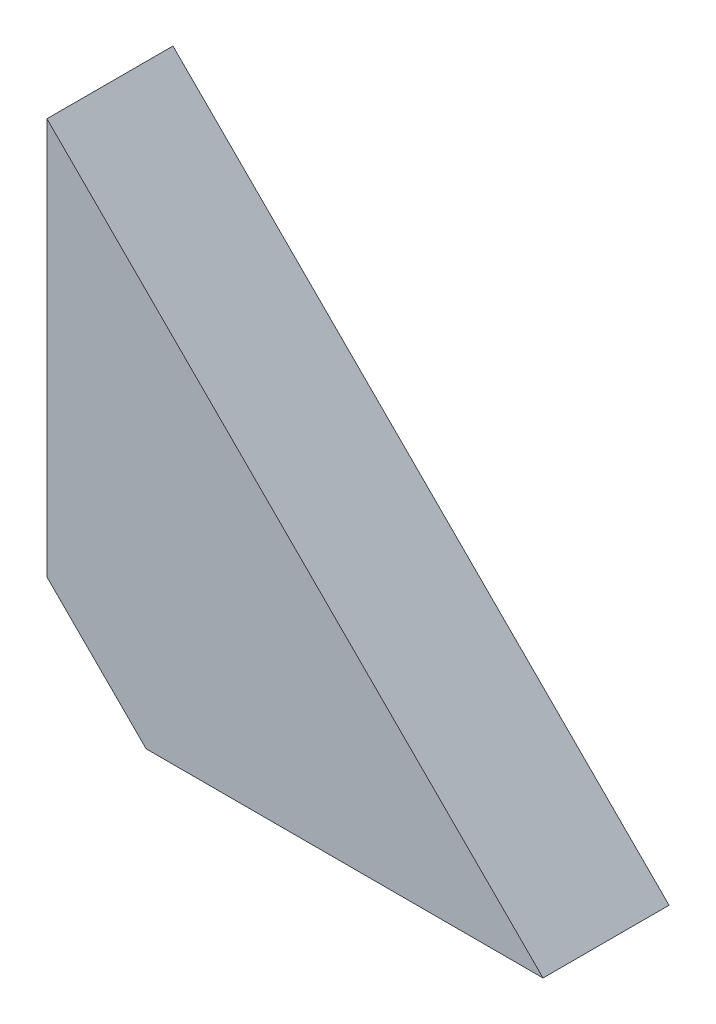
SolidWorks part; units mm, degrees
material "ASTM A36 Aço"
ref_plane "Plano frontal" through (0, 0, 0) normal (0, 0, 1) x (1, 0, 0)
ref_plane "Plano superior" through (0, 0, 0) normal (0, 1, 0) x (1, 0, 0)
ref_plane "Plano direito" through (0, 0, 0) normal (1, 0, 0) x (0, 0, -1)
sketch "Esboço1" plane through (0, 0, 0) normal (0, 0, 1) x (1, 0, 0)
  line L0 (0, 50) -> (50, 0)
  line L1 (0, 0) -> (50, 0)
  line L2 (0, 0) -> (0, 50)
  line L3 (0, 50) -> (50, 50) construction
  line L4 (50, 0) -> (50, 50) construction
  dimension "D1" = 50
base flange "Flange-base1" sketch "Esboço1" thickness 12.7 reverse thickness direction no parameters "D1"=2.2
chamfer "Chanfro1" distance 10 angle 45 1 edges at (0, 0, -6.35)
sketch "Curva-Linhas1" [suppressed] plane through (0, 0, 0) normal (0, 1, 0) x (1, 0, 0)
sketch "Caixa delimitadora1" [suppressed] plane through (0, 0, 0) normal (0, 1, 0) x (1, 0, 0)
sheet metal parameters "Chapa metálica3" thickness 12.7 parameters "D1"=2.2
flat pattern "Padrão-Plano3" [suppressed]
sketch "Curva-Linhas2" plane through (0, 0, 0) normal (0, 1, 0) x (1, 0, 0)
sketch3d "Caixa delimitadora2" [suppressed]
  line L0 (0, 50, 0) -> (50, 0, 0) construction
  line L1 (-20, 30, 0) -> (30, -20, 0) construction
  line L2 (0, 50, 0) -> (-20, 30, 0) construction
  line L3 (50, 0, 0) -> (30, -20, 0) construction
